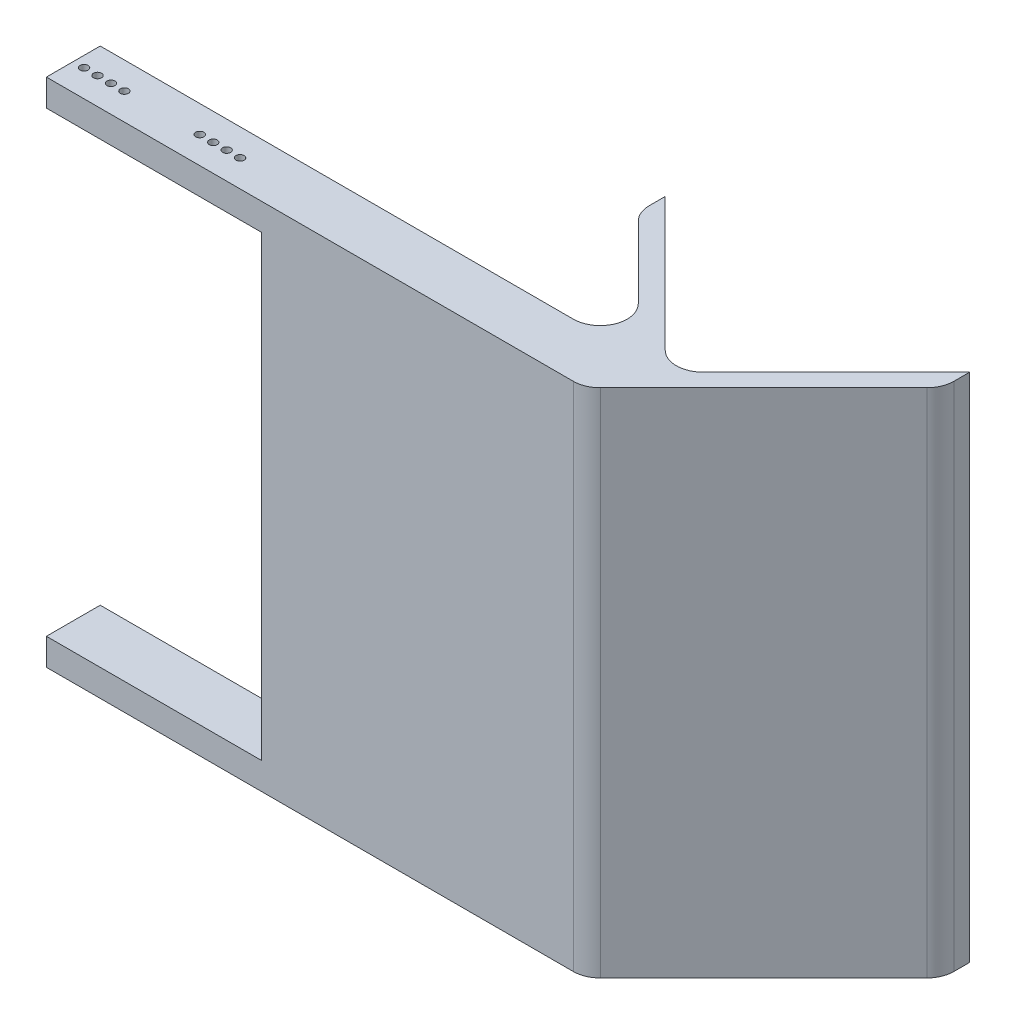
SolidWorks part; units mm, degrees
other "Marquage1"
sketch "Esquisse6" plane through (-75, 0, -38.2843) normal (-0.024, -0.0063, -0.9997) x (-0.9942, -0.1051, 0.0245)
ref_plane "Front Plane" through (0, 0, 0) normal (0, 0, 1) x (1, 0, 0)
ref_plane "Top Plane" through (0, 0, 0) normal (0, 1, 0) x (1, 0, 0)
ref_plane "Right Plane" through (0, 0, 0) normal (1, 0, 0) x (0, 0, -1)
sketch "Sketch1" plane through (0, 0, 0) normal (0, 1, 0) x (1, 0, 0)
  line L0 (-55, 0) -> (55, 0) construction
  line L1 (30, 0) -> (-75, 0)
  line L4 (-75, 0) -> (-75, 10)
  line L5 (30, 10) -> (58.2843, 38.2843)
  line L6 (58.2843, 38.2843) -> (58.2843, 33.2843)
  line L7 (58.2843, 33.2843) -> (35, 10)
  line L8 (30, 10) -> (1.7157, 38.2843)
  line L9 (1.7157, 38.2843) -> (1.7157, 33.2843)
  line L10 (1.7157, 33.2843) -> (25, 10)
  line L11 (35, 10) -> (25, 0)
  line L12 (-75, 10) -> (25, 10)
  line L13 (25, 0) -> (-75, 0)
  dimension "D10" = 10
  dimension "D1" = 30
  dimension "D2" = 30
  dimension "D3" = 75
  dimension "D4" = 10
  dimension "D5" = 33.2843
  dimension "D6" = 58.2843
  dimension "D7" = 225
  dimension "D8" = 33.2843
  dimension "D9" = 28.2843
  dimension "D11" = 90
  dimension "D12" = 45
  dimension "D13" = 5
extrude "Boss-Extrude3" add sketch "Sketch1" along normal blind 95 contours L4 L12 L10 L9 L8 L5 L6 L7 L11 L13
fillet "Fillet7" radius 5 1 edges at (30, 47.5, -10)
fillet "Fillet8" radius 5 1 edges at (25, 47.5, -10)
fillet "Fillet9" radius 5 2 edges at (58.2843, 47.5, -33.2843) (1.7157, 47.5, -33.2843)
fillet "Fillet10" radius 5 1 edges at (25, 47.5, 0)
sketch "Esquisse3" plane through (0, 0, -10) normal (0, 0, -1) x (-1, 0, 0)
  line L0 (75, 95) -> (75, 0) construction
  line L1 (75, 5) -> (45, 5)
  line L2 (75, 5) -> (75, 90)
  line L3 (75, 90) -> (45, 90)
  line L4 (45, 5) -> (45, 90)
  line L5 (75, 0) -> (-12.9289, 0) construction
  line L6 (75, 95) -> (-12.9289, 95) construction
  dimension "D1" = 5
  dimension "D2" = 5
  dimension "D3" = 30
extrude "Enlèv. mat.-Extru.1" cut sketch "Esquisse3" against normal through all contours L2 L1 L4 L3
sketch "Esquisse4" plane through (0, 90, 0) normal (0, -1, 0) x (1, 0, 0)
  line L0 (-75, -10) -> (-45, -10) construction
  line L1 (-75, 0) -> (-75, -10) construction
  line L2 (-75, 0) -> (-45, 0) construction
  circle A0 centre (-73, -5) radius 0.75
  circle A1 centre (-68, -5) radius 0.75
  circle A2 centre (-70.5, -5) radius 0.75
  circle A3 centre (-65.5, -5) radius 0.75
  circle A4 centre (-46.5, -5) radius 0.75
  circle A5 centre (-49, -5) radius 0.75
  circle A7 centre (-51.5, -5) radius 0.75
  dimension "D1" = 1.5
  dimension "D2" = 5
  dimension "D11" = 5
  dimension "D3" = 2
  dimension "D4" = 2.5
  dimension "D5" = 2.5
  dimension "D6" = 2.5
  dimension "D7" = 5
  dimension "D8" = 5
  dimension "D9" = 5
  dimension "D10" = 14
  dimension "D12" = 10
  dimension "D13" = 2.5
  dimension "D14" = 2.5
sketch "Esquisse5" plane through (0, 0, -10) normal (0, 0, -1) x (-1, 0, 0)
  line L1 (45, 5) -> (35, 5)
  line L2 (45, 5) -> (45, 65)
  line L3 (45, 65) -> (35, 65)
  line L4 (35, 5) -> (35, 65)
  dimension "D1" = 10
extrude "Enlèv. mat.-Extru.2" cut sketch "Esquisse5" against normal through all contours L2 L1 L4 L3
sketch "Esquisse13" plane through (0, 90, 0) normal (0, -1, 0) x (-1, 0, 0)
  line L0 (75, 10) -> (45, 10) construction
  circle A0 centre (44, 5) radius 0.75
  dimension "D1" = 2.5
  dimension "D2" = 5
extrude "Enlèv. mat.-Extru.3" cut sketch "Esquisse13" against normal blind 10
extrude "Enlèv. mat.-Extru.6" cut sketch "Esquisse4" against normal blind 10
sketch "Esquisse14" plane through (0, 0, -10) normal (0, 0, -1) x (-1, 0, 0)
  line L0 (45, 65) -> (35, 65) construction
  line L1 (45, 90) -> (35, 90)
  line L2 (45, 90) -> (45, 65)
  line L3 (45, 65) -> (35, 65)
  line L4 (35, 90) -> (35, 65)
extrude "Enlèv. mat.-Extru.7" cut sketch "Esquisse14" against normal through all
